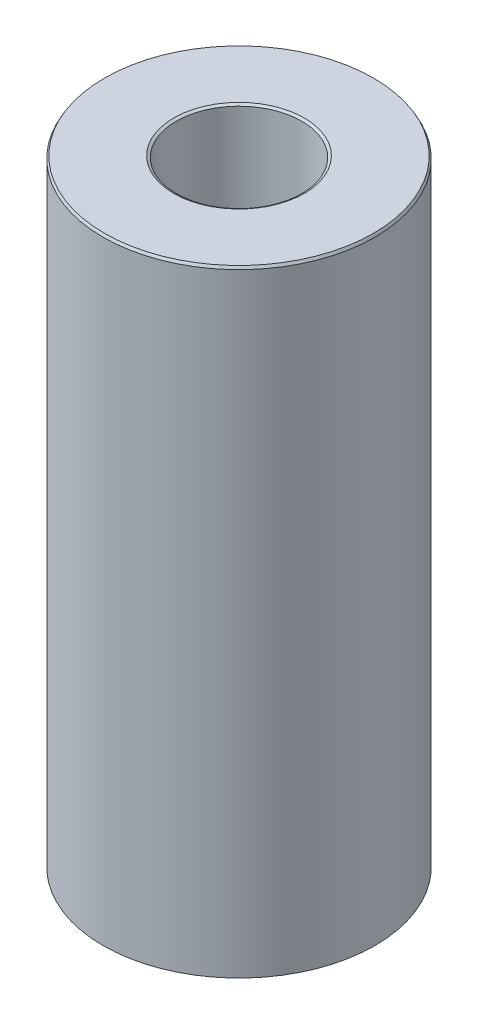
SolidWorks part; units mm, degrees
ref_plane "Front Plane" through (0, 0, 0) normal (0, 0, 1) x (1, 0, 0)
ref_plane "Top Plane" through (0, 0, 0) normal (0, 1, 0) x (1, 0, 0)
ref_plane "Right Plane" through (0, 0, 0) normal (1, 0, 0) x (0, 0, -1)
sketch "Sketch1" plane through (0, 0, 0) normal (0, 1, 0) x (1, 0, 0)
  circle A0 centre (0, 0) radius 55
  dimension "SLEEVE_OD" = 110
extrude "Boss-Extrude1" add sketch "Sketch1" along normal blind 249.803
sketch "Sketch2" plane through (0, 0, 0) normal (0, 1, 0) x (1, 0, 0)
  circle A0 centre (0, 0) radius 25.3873
  dimension "BORE_D" = 50.7747
extrude "Cut-Extrude1" cut sketch "Sketch2" along normal through all
chamfer "Chamfer1" distance 1.0379 angle 30 4 edges at (0, 249.803, 25.3873) (0, 0, 25.3873) (0, 0, 55) (0, 249.803, 55) first distance on face at (0, 249.803, 25.3873) first distance on face at (0, 0, 25.3873) first distance on face at (0, 249.803, 55)
